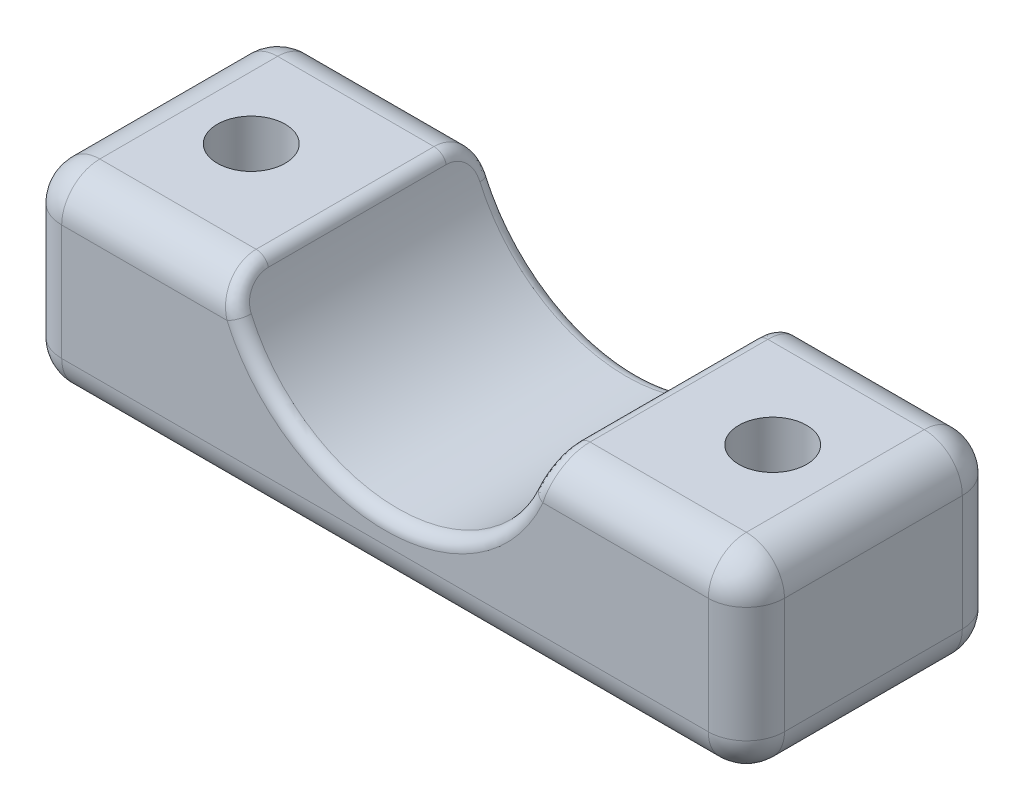
SolidWorks part; units mm, degrees
material "PLA ABS"
ref_plane "Front Plane" through (0, 0, 0) normal (0, 0, 1) x (1, 0, 0)
ref_plane "Top Plane" through (0, 0, 0) normal (0, 1, 0) x (1, 0, 0)
ref_plane "Right Plane" through (0, 0, 0) normal (1, 0, 0) x (0, 0, -1)
sketch "Sketch1" plane through (0, 0, 0) normal (0, 0, 1) x (1, 0, 0)
  line L0 (16.002, 22.352) -> (36.1315, 22.352)
  line L1 (-36.1315, 0) -> (36.1315, 0)
  line L2 (-36.1315, 0) -> (-36.1315, 22.352)
  line L3 (-36.1315, 22.352) -> (-16.002, 22.352)
  line L4 (36.1315, 0) -> (36.1315, 22.352)
  arc A0 (-16.002, 22.352) -> (16.002, 22.352) centre (0, 22.352) ccw
  dimension "D1" = 32.004
  dimension "D2" = 72.263
  dimension "D3" = 6.35
extrude "Boss-Extrude1" add sketch "Sketch1" along normal mid plane 25.4
sketch "Sketch2" plane through (0, 22.352, 0) normal (0, 1, 0) x (1, 0, 0)
  line L0 (-26.0668, 12.7) -> (-26.0667, -12.7) construction
  line L1 (-16.002, 12.7) -> (-36.1315, 12.7) construction
  line L2 (-16.002, -12.7) -> (-36.1315, -12.7) construction
  line L3 (0, 0) -> (0, 12.7) construction
  line L4 (16.002, 12.7) -> (-16.002, 12.7) construction
  circle A0 centre (-26.0668, 0) radius 3.3909
  circle A1 centre (26.0668, 0) radius 3.3909
  dimension "D1" = 6.7818
extrude "Cut-Extrude1" cut sketch "Sketch2" against normal through all
sketch "Sketch3" plane through (0, 0, 12.7) normal (0, 0, 1) x (1, 0, 0)
  line L0 (-16.002, 22.352) -> (-36.1315, 22.352) construction
  line L1 (-36.1315, 26.3528) -> (36.1315, 26.3528)
  line L2 (-36.1315, 26.3528) -> (-36.1315, 19.177)
  line L3 (-36.1315, 19.177) -> (36.1315, 19.177)
  line L4 (36.1315, 26.3528) -> (36.1315, 19.177)
  line L5 (-36.1315, 22.352) -> (-36.1315, 0) construction
  line L6 (36.1315, 0) -> (36.1315, 22.352) construction
  dimension "D1" = 3.175
extrude "Cut-Extrude2" cut sketch "Sketch3" against normal through all
sketch "Sketch6" plane through (0, 0, 0) normal (0, -1, 0) x (1, 0, 0)
  line L0 (0, 12.7) -> (0, -12.7) construction
  line L1 (-36.1315, 12.7) -> (36.1315, 12.7) construction
  line L2 (-36.1315, -12.7) -> (36.1315, -12.7) construction
  circle A0 centre (-26.0668, 0) radius 5.6833
  circle A1 centre (26.0668, 0) radius 5.6833
  dimension "D1" = 11.3665
extrude "Cut-Extrude3" cut sketch "Sketch6" against normal blind 4.0716
fillet "Fillet3" radius 3.81 14 edges at (-36.1315, 0, 0) (-36.1315, 9.5885, -12.7) (-36.1315, 19.177, 0) (-36.1315, 9.5885, 12.7) (36.1315, 0, 0) (36.1315, 9.5885, 12.7) (36.1315, 19.177, 0) (36.1315, 9.5885, -12.7) (-25.9077, 19.177, 12.7) (25.9077, 19.177, 12.7) (0, 0, 12.7) (0, 0, -12.7) (25.9077, 19.177, -12.7) (-25.9077, 19.177, -12.7)
fillet "Fillet4" radius 1.27 8 edges at (15.3443, 17.8116, 11.8123) (15.6839, 19.177, 0) (15.5012, 18.3799, -11.2221) (0, 6.35, -12.7) (-15.3443, 17.8116, -11.8123) (-15.6839, 19.177, 0) (-15.5012, 18.3799, 11.2221) (0, 6.35, 12.7)
